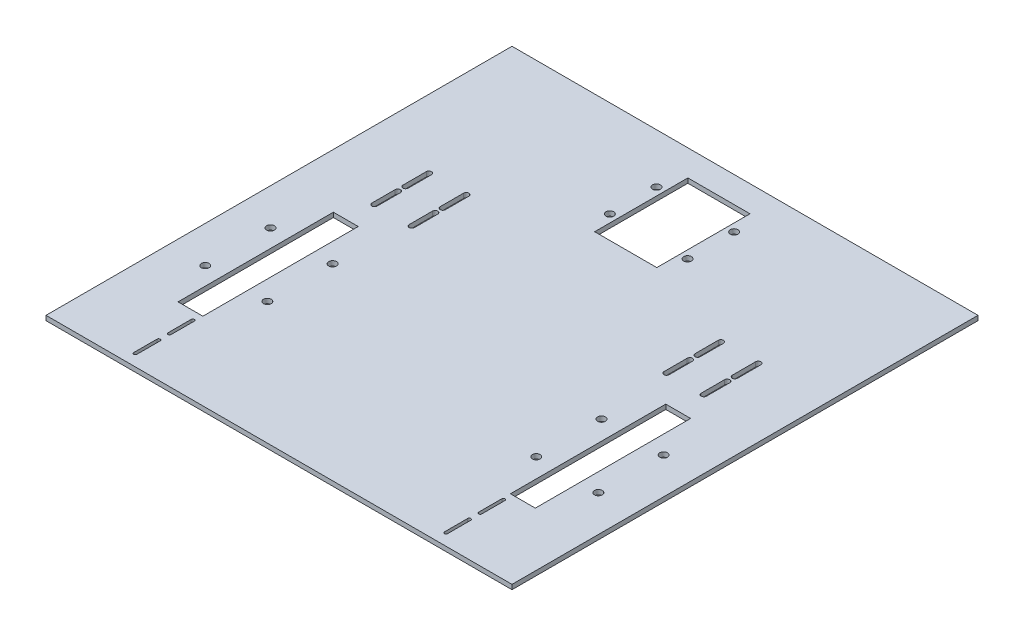
SolidWorks part; units mm, degrees
ref_plane "Front Plane" through (0, 0, 0) normal (0, 0, 1) x (1, 0, 0)
ref_plane "Top Plane" through (0, 0, 0) normal (0, 1, 0) x (1, 0, 0)
ref_plane "Right Plane" through (0, 0, 0) normal (1, 0, 0) x (0, 0, -1)
sketch "Sketch1" plane through (0, 0, 0) normal (0, 1, 0) x (1, 0, 0)
  line L0 (0, 0) -> (0, 150) construction
  line L5 (-150, -150) -> (150, -150)
  line L6 (-150, -150) -> (-150, 150)
  line L7 (-150, 150) -> (150, 150)
  line L8 (150, -150) -> (150, 150)
  line L9 (-150, -150) -> (150, 150) construction
  line L10 (-150, 150) -> (150, -150) construction
  line L11 (0, 0) -> (0, -150) construction
  point P0 (0, 0)
  dimension "D1" = 300
  dimension "D2" = 300
extrude "Boss-Extrude1" add sketch "Sketch1" along normal blind 3
sketch "Sketch2" plane through (0, 3, 0) normal (0, 1, 0) x (1, 0, 0)
  line L0 (-107, -49.9975) -> (-150, -49.9975) construction
  line L1 (-115, 0.0025) -> (-99, 0.0025)
  line L2 (-115, 0.0025) -> (-115, -99.9975)
  line L3 (-115, -99.9975) -> (-99, -99.9975)
  line L4 (-99, 0.0025) -> (-99, -99.9975)
  line L5 (-115, 0.0025) -> (-99, -99.9975) construction
  line L6 (-115, -99.9975) -> (-99, 0.0025) construction
  line L7 (-150, 150) -> (-150, -150) construction
  point P0 (-107, -49.9975)
  dimension "D1" = 43
sketch "Sketch3" plane through (0, 3, 0) normal (0, 1, 0) x (1, 0, 0)
  line L0 (106.9979, -50.0021) -> (150, -50.0021) construction
  line L1 (98.9979, -0.0021) -> (114.9979, -0.0021)
  line L2 (98.9979, -0.0021) -> (98.9979, -100.0021)
  line L3 (98.9979, -100.0021) -> (114.9979, -100.0021)
  line L4 (114.9979, -0.0021) -> (114.9979, -100.0021)
  line L5 (98.9979, -0.0021) -> (114.9979, -100.0021) construction
  line L6 (98.9979, -100.0021) -> (114.9979, -0.0021) construction
  line L7 (150, -150) -> (150, 150) construction
  point P0 (106.9979, -50.0021)
  dimension "D1" = 43.0021
sketch "Sketch4" plane through (0, 3, 0) normal (0, 1, 0) x (1, 0, 0)
  line L0 (-150, -49.99) -> (-115, -49.99) construction
  line L1 (-150, 150) -> (-150, -150) construction
  line L2 (-115, 0.0025) -> (-115, -99.9975) construction
  line L3 (114.9979, -50.0021) -> (150, -50.0021) construction
  line L4 (114.9979, -0.0021) -> (114.9979, -100.0021) construction
  line L5 (150, -150) -> (150, 150) construction
  line L6 (106.9979, -100.0021) -> (106.9979, -150) construction
  line L7 (98.9979, -100.0021) -> (114.9979, -100.0021) construction
  line L8 (-150, -150) -> (150, -150) construction
  line L9 (-107, -99.9975) -> (-107, -150) construction
  line L10 (-115, -99.9975) -> (-99, -99.9975) construction
  dimension "D1" = 35
  dimension "D2" = 35.0021
  dimension "D3" = 49.9979
  dimension "D4" = 50.0025
extrude "Cut-Extrude2" cut sketch "Sketch2" against normal blind 3
extrude "Cut-Extrude3" cut sketch "Sketch3" against normal blind 3
sketch "Sketch5" plane through (0, 3, 0) normal (0, 1, 0) x (1, 0, 0)
  line L1 (-19.9998, 133.2218) -> (20.0002, 133.2218)
  line L2 (-19.9998, 133.2218) -> (-19.9998, 73.2218)
  line L3 (-19.9998, 73.2218) -> (20.0002, 73.2218)
  line L4 (20.0002, 133.2218) -> (20.0002, 73.2218)
  line L5 (-19.9998, 133.2218) -> (20.0002, 73.2218) construction
  line L6 (-19.9998, 73.2218) -> (20.0002, 133.2218) construction
  point P0 (0.0002, 103.2218)
extrude "Cut-Extrude4" cut sketch "Sketch5" against normal blind 3
sketch "Sketch6" plane through (0, 3, 0) normal (0, 1, 0) x (1, 0, 0)
  line L0 (-126.4658, -29.0191) -> (-126.4658, -71.0191) construction
  line L1 (126.6814, -29.0751) -> (126.6814, -71.0751) construction
  line L2 (-86.4658, -29.0191) -> (-86.4658, -71.0191) construction
  line L3 (86.6814, -29.0751) -> (86.6814, -71.0751) construction
  line L4 (-25, 118) -> (-25, 88) construction
  line L5 (-25, 88) -> (25, 88) construction
  line L6 (-126.4658, -29.0191) -> (-86.4658, -29.0191) construction
  line L8 (86.6814, -29.0751) -> (126.6814, -29.0751) construction
  line L9 (-126.4658, -29.0191) -> (-86.4658, -71.0191) construction
  line L10 (-86.4658, -29.0191) -> (-126.4658, -71.0191) construction
  line L11 (-115, -49.99) -> (-106.4658, -50.0191) construction
  line L12 (86.6814, -29.0751) -> (126.6814, -71.0751) construction
  line L13 (126.6814, -29.0751) -> (86.6814, -71.0751) construction
  line L14 (114.9979, -50.0021) -> (106.6814, -50.0751) construction
  line L15 (-25, 118) -> (25, 118) construction
  line L16 (25, 118) -> (25, 88) construction
  circle A0 centre (-126.4658, -29.0191) radius 2.5
  circle A1 centre (-86.4658, -29.0191) radius 2.5
  circle A2 centre (-126.4658, -71.0191) radius 2.5
  circle A3 centre (-86.4658, -71.0191) radius 2.5
  circle A4 centre (86.6814, -29.0751) radius 2.5
  circle A5 centre (86.6814, -71.0751) radius 2.5
  circle A6 centre (126.6814, -29.0751) radius 2.5
  circle A7 centre (126.6814, -71.0751) radius 2.5
  circle A8 centre (-25, 118) radius 2.5
  circle A9 centre (-25, 88) radius 2.5
  circle A10 centre (25, 118) radius 2.5
  circle A11 centre (25, 88) radius 2.5
  dimension "D1" = 42
  dimension "D2" = 42
  dimension "D3" = 42
  dimension "D4" = 42
  dimension "D5" = 50
  dimension "D6" = 30
  dimension "D7" = 40
  dimension "D8" = 40
extrude "Cut-Extrude5" cut sketch "Sketch6" against normal blind 3
sketch "Sketch7" plane through (0, 3, 0) normal (0, 1, 0) x (1, 0, 0)
  line L0 (-106, 52.5) -> (-106, 37.5) construction
  line L1 (-104.3, 52.5) -> (-104.3, 37.5)
  line L2 (-107.7, 52.5) -> (-107.7, 37.5)
  line L3 (-106, 32.5) -> (-106, 17.5) construction
  line L4 (-104.3, 32.5) -> (-104.3, 17.5)
  line L5 (-107.7, 32.5) -> (-107.7, 17.5)
  line L6 (-82, 52.5) -> (-82, 37.5) construction
  line L7 (-80.3, 52.5) -> (-80.3, 37.5)
  line L8 (-83.7, 52.5) -> (-83.7, 37.5)
  line L9 (-82, 32.5) -> (-82, 17.5) construction
  line L10 (-80.3, 32.5) -> (-80.3, 17.5)
  line L11 (-83.7, 32.5) -> (-83.7, 17.5)
  line L14 (82, 52.5) -> (82, 37.5) construction
  line L15 (83.7, 52.5) -> (83.7, 37.5)
  line L16 (80.3, 52.5) -> (80.3, 37.5)
  line L17 (82, 32.5) -> (82, 17.5) construction
  line L18 (83.7, 32.5) -> (83.7, 17.5)
  line L19 (80.3, 32.5) -> (80.3, 17.5)
  line L20 (106, 52.5) -> (106, 37.5) construction
  line L21 (107.7, 52.5) -> (107.7, 37.5)
  line L22 (104.3, 52.5) -> (104.3, 37.5)
  line L23 (106, 32.5) -> (106, 17.5) construction
  line L24 (107.7, 32.5) -> (107.7, 17.5)
  line L25 (104.3, 32.5) -> (104.3, 17.5)
  arc A0 (-104.3, 52.5) -> (-107.7, 52.5) centre (-106, 52.5) ccw
  arc A1 (-107.7, 37.5) -> (-104.3, 37.5) centre (-106, 37.5) ccw
  arc A2 (-104.3, 32.5) -> (-107.7, 32.5) centre (-106, 32.5) ccw
  arc A3 (-107.7, 17.5) -> (-104.3, 17.5) centre (-106, 17.5) ccw
  arc A4 (-80.3, 52.5) -> (-83.7, 52.5) centre (-82, 52.5) ccw
  arc A5 (-83.7, 37.5) -> (-80.3, 37.5) centre (-82, 37.5) ccw
  arc A6 (-80.3, 32.5) -> (-83.7, 32.5) centre (-82, 32.5) ccw
  arc A7 (-83.7, 17.5) -> (-80.3, 17.5) centre (-82, 17.5) ccw
  arc A8 (83.7, 52.5) -> (80.3, 52.5) centre (82, 52.5) ccw
  arc A9 (80.3, 37.5) -> (83.7, 37.5) centre (82, 37.5) ccw
  arc A10 (83.7, 32.5) -> (80.3, 32.5) centre (82, 32.5) ccw
  arc A11 (80.3, 17.5) -> (83.7, 17.5) centre (82, 17.5) ccw
  arc A12 (107.7, 52.5) -> (104.3, 52.5) centre (106, 52.5) ccw
  arc A13 (104.3, 37.5) -> (107.7, 37.5) centre (106, 37.5) ccw
  arc A14 (107.7, 32.5) -> (104.3, 32.5) centre (106, 32.5) ccw
  arc A15 (104.3, 17.5) -> (107.7, 17.5) centre (106, 17.5) ccw
  point P2 (-106, 45)
  point P9 (-106, 25)
  point P16 (-82, 45)
  point P23 (-82, 25)
  point P34 (82, 45)
  point P41 (82, 25)
  point P48 (106, 45)
  point P55 (106, 25)
extrude "Cut-Extrude6" cut sketch "Sketch7" against normal blind 3
sketch "Sketch8" plane through (0, 3, 0) normal (0, 1, 0) x (1, 0, 0)
  line L0 (-100, -105.5) -> (-100, -120.5) construction
  line L1 (-99, -105.5) -> (-99, -120.5)
  line L2 (-101, -105.5) -> (-101, -120.5)
  line L3 (-100, -127.5) -> (-100, -142.5) construction
  line L4 (-99, -127.5) -> (-99, -142.5)
  line L5 (-101, -127.5) -> (-101, -142.5)
  line L18 (100, -105.5) -> (100, -120.5) construction
  line L19 (101, -105.5) -> (101, -120.5)
  line L20 (99, -105.5) -> (99, -120.5)
  line L21 (100, -127.5) -> (100, -142.5) construction
  line L22 (101, -127.5) -> (101, -142.5)
  line L23 (99, -127.5) -> (99, -142.5)
  arc A0 (-99, -105.5) -> (-101, -105.5) centre (-100, -105.5) ccw
  arc A1 (-101, -120.5) -> (-99, -120.5) centre (-100, -120.5) ccw
  arc A2 (-99, -127.5) -> (-101, -127.5) centre (-100, -127.5) ccw
  arc A3 (-101, -142.5) -> (-99, -142.5) centre (-100, -142.5) ccw
  arc A12 (101, -105.5) -> (99, -105.5) centre (100, -105.5) ccw
  arc A13 (99, -120.5) -> (101, -120.5) centre (100, -120.5) ccw
  arc A14 (101, -127.5) -> (99, -127.5) centre (100, -127.5) ccw
  arc A15 (99, -142.5) -> (101, -142.5) centre (100, -142.5) ccw
  point P2 (-100, -113)
  point P9 (-100, -135)
  point P28 (0, 0)
  point P29 (0, 0)
  point P46 (100, -113)
  point P53 (100, -135)
  point P58 (0, 0)
  point P59 (0, 0)
  point P60 (0, 0)
extrude "Cut-Extrude7" cut sketch "Sketch8" against normal blind 3
